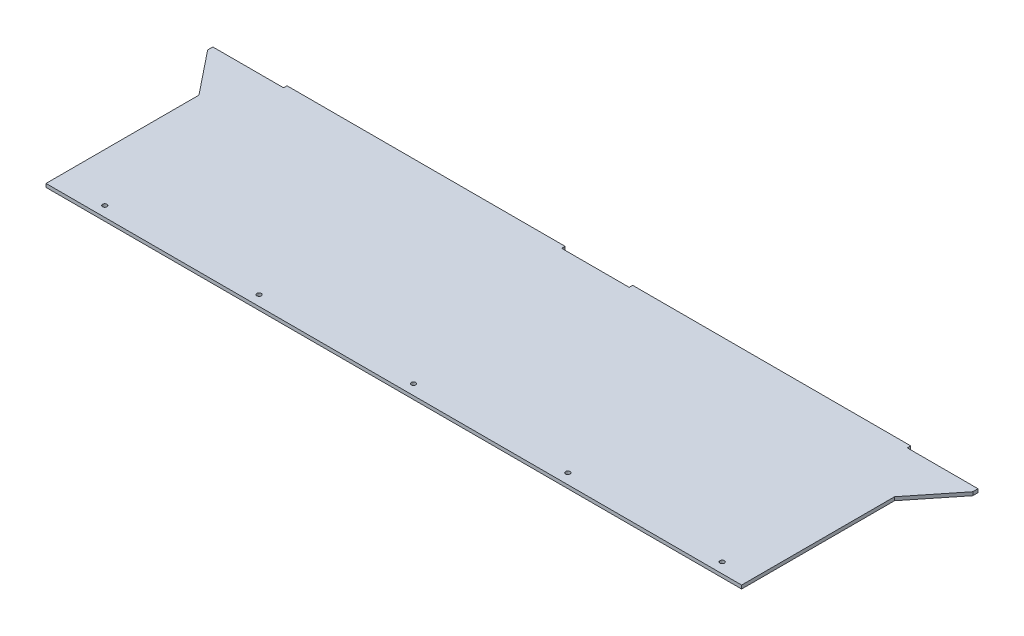
SolidWorks part; units mm, degrees
material "6061-T6 (SS)"
ref_plane "X-Y Datum" through (0, 0, 0) normal (0, 0, 1) x (1, 0, 0)
ref_plane "X-Z Datum" through (0, 0, 0) normal (0, 1, 0) x (1, 0, 0)
ref_plane "Y-Z Datum" through (0, 0, 0) normal (1, 0, 0) x (0, 0, -1)
sketch "Sketch1" plane through (0, 0, 0) normal (0, 1, 0) x (1, 0, 0)
  line L1 (-317.6778, 92.075) -> (317.6778, 92.075)
  line L2 (-317.6778, 92.075) -> (-317.6778, -92.075)
  line L3 (-317.6778, -92.075) -> (317.6778, -92.075)
  line L4 (317.6778, 92.075) -> (317.6778, -92.075)
  line L5 (-317.6778, 92.075) -> (317.6778, -92.075) construction
  line L6 (-317.6778, -92.075) -> (317.6778, 92.075) construction
  point P0 (0, 0)
  dimension "D1" = 635.3556
  dimension "D2" = 184.15
extrude "Boss-Extrude1" add sketch "Sketch1" along normal mid plane 3.175
sketch "Sketch2" plane through (0, 0, -92.075) normal (0, 0, -1) x (-1, 0, 0)
  line L20 (-317.6778, -1.5875) -> (317.6778, -1.5875) construction
  line L21 (-284.8229, -1.5875) -> (-30.8229, -1.5875)
  line L22 (30.8229, -1.5875) -> (284.8229, -1.5875)
  line L40 (30.8229, -1.5875) -> (30.8229, 1.5875)
  line L41 (30.8229, 1.5875) -> (284.8229, 1.5875)
  line L42 (284.8229, 1.5875) -> (284.8229, -1.5875)
  line L56 (-284.8229, -1.5875) -> (-284.8229, 1.5875)
  line L57 (-284.8229, 1.5875) -> (-30.8229, 1.5875)
  line L58 (-30.8229, 1.5875) -> (-30.8229, -1.5875)
extrude "Boss-Extrude2" add sketch "Sketch2" along normal blind 3.175
sketch "Sketch3" plane through (0, -1.5875, 0) normal (0, -1, 0) x (1, 0, 0)
  line L0 (317.6778, -92.075) -> (349.4278, -92.075)
  line L1 (349.4278, -92.075) -> (349.4278, -87.3125)
  line L3 (349.4278, -87.3125) -> (317.6778, -47.625)
  line L4 (317.6778, 92.075) -> (317.6778, -92.075) construction
  line L17 (317.6778, -92.075) -> (317.6778, 92.075)
  line L18 (317.6778, 92.075) -> (-317.6778, 92.075)
  line L19 (-317.6778, 92.075) -> (-317.6778, -92.075)
  line L20 (-317.6778, -92.075) -> (-284.8229, -92.075)
  line L21 (-284.8229, -92.075) -> (-284.8229, -95.25)
  line L22 (-284.8229, -95.25) -> (-30.8229, -95.25)
  line L23 (-30.8229, -95.25) -> (-30.8229, -92.075)
  line L24 (-30.8229, -92.075) -> (30.8229, -92.075)
  line L25 (30.8229, -92.075) -> (30.8229, -95.25)
  line L26 (30.8229, -95.25) -> (284.8229, -95.25)
  line L27 (284.8229, -95.25) -> (284.8229, -92.075)
  line L28 (284.8229, -92.075) -> (317.6778, -92.075)
  line L29 (317.6778, -92.075) -> (317.6778, -47.625)
  dimension "D1" = 31.75
  dimension "D2" = 4.7625
  dimension "D3" = 44.45
  dimension "D4" = 0
extrude "Boss-Extrude3" add sketch "Sketch3" against normal blind 3.175
mirror "Mirror1" about plane through (0, 0, 0) normal (1, 0, 0) of "Boss-Extrude3"
sketch "Sketch4" plane through (0, 1.5875, 0) normal (0, 1, 0) x (1, 0, 0)
  line L0 (290.4998, -92.075) -> (290.4998, -82.677)
  line L1 (-317.6778, -92.075) -> (317.6778, -92.075) construction
  line L2 (290.4998, -82.677) -> (317.6778, -82.677)
  line L3 (317.6778, -92.075) -> (317.6778, 47.625) construction
  circle A0 centre (290.4998, -82.677) radius 2.025
extrude "Cut-Extrude1" cut sketch "Sketch4" against normal blind 10 contours L2 A0 L0 | L0 A0 L2 region at (290.2133, 1.5875, 82.3905) region at (291.3592, 1.5875, 83.5364)
pattern_linear "LPattern1" count 5 spacing 140.97 along (-1, 0, 0) of "Cut-Extrude1"
